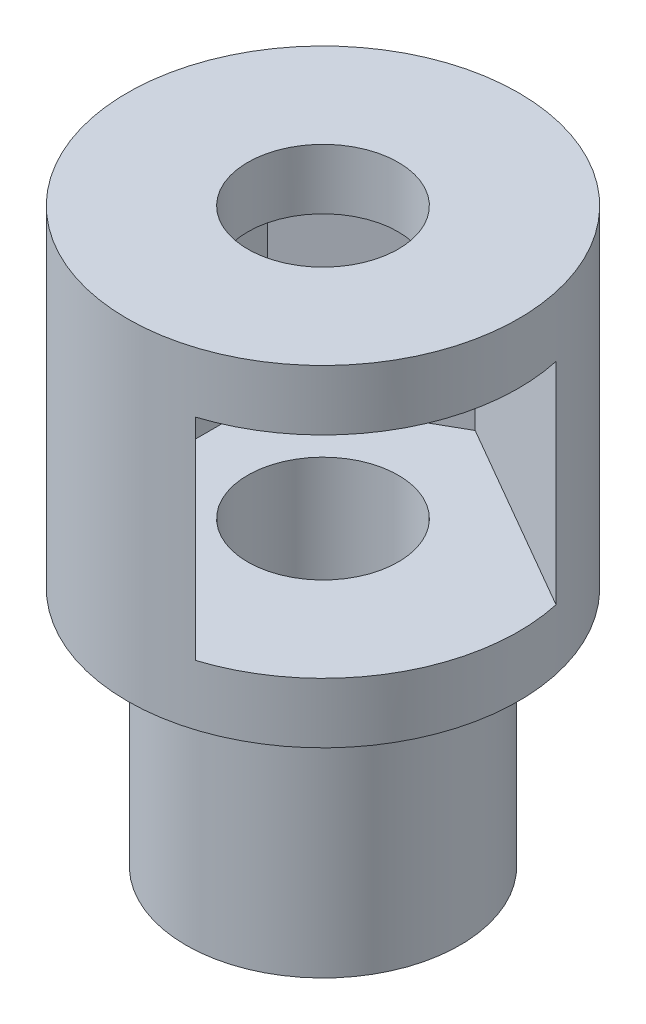
SolidWorks part; units mm, degrees
ref_plane "Front Plane" through (0, 0, 0) normal (0, 0, 1) x (1, 0, 0)
ref_plane "Top Plane" through (0, 0, 0) normal (0, 1, 0) x (1, 0, 0)
ref_plane "Right Plane" through (0, 0, 0) normal (1, 0, 0) x (0, 0, -1)
sketch "Sketch1" plane through (0, 0, 0) normal (0, 1, 0) x (1, 0, 0)
  circle A0 centre (0, 0) radius 4.55
  dimension "D1" = 9.1
extrude "Boss-Extrude1" add sketch "Sketch1" along normal blind 8 contours A0
sketch "Sketch2" plane through (0, 8, 0) normal (0, 1, 0) x (1, 0, 0)
  circle A0 centre (0, 0) radius 2.5
extrude "Cut-Extrude1" cut sketch "Sketch2" against normal blind 8
sketch "Sketch3" plane through (0, 8, 0) normal (0, 1, 0) x (1, 0, 0)
  circle A0 centre (0, 0) radius 6.5
  dimension "D1" = 13
extrude "Boss-Extrude4" add sketch "Sketch3" along normal blind 9 contours A0
sketch "Sketch5" plane through (0, 17, 0) normal (0, 1, 0) x (1, 0, 0)
  line L0 (0, 0) -> (4.3938, 0) construction
  line L3 (4.3938, 2.521) -> (4.3938, -2.521) construction
  line L5 (4.3938, -2.521) -> (-0.0062, -5.0614) construction
  line L9 (-0.0062, -5.0614) -> (-4.4062, -2.521) construction
  line L12 (-4.4062, -2.521) -> (-4.4062, 2.5597)
  line L13 (-4.4062, 2.5597) -> (-0.0062, 5.0614)
  line L14 (-0.0062, 5.0614) -> (4.3938, 2.521) construction
  line L15 (-4.1854, -2.6484) -> (43297.0847, -25002.6484) construction
  line L16 (0.0916, 5.0049) -> (43301.3618, -24994.9951) construction
  line L17 (7.8193, 0.5434) -> (3.436, -7.0487)
  line L18 (-0.0062, 5.0614) -> (7.8193, 0.5434)
  line L19 (3.436, -7.0487) -> (-4.4062, -2.521)
  circle A0 centre (0, 0) radius 6.5 construction
  point P6 (4.3938, 0)
  dimension "D1" = 120
extrude "Cut-Extrude2" cut sketch "Sketch5" against normal blind 7
sketch "Sketch6" plane through (0, 17, 0) normal (0, 1, 0) x (1, 0, 0)
  circle A0 centre (0, 0) radius 6.5
  dimension "D1" = 13
extrude "Boss-Extrude5" add sketch "Sketch6" along normal blind 2
sketch "Sketch7" plane through (0, 0, 0) normal (0, -1, 0) x (1, 0, 0)
  circle A0 centre (0, 0) radius 2.5
extrude "Cut-Extrude3" cut sketch "Sketch7" against normal through all
